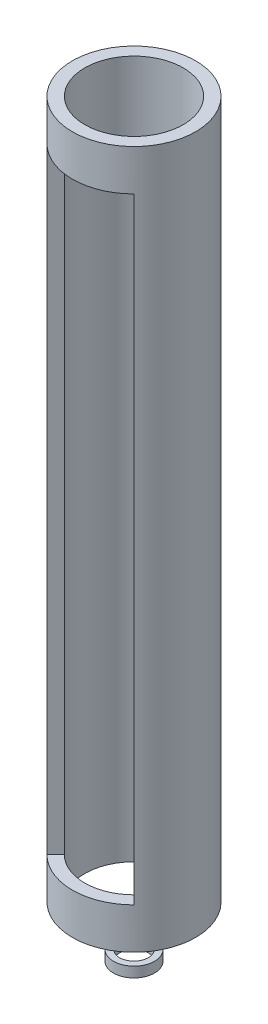
SolidWorks part; units mm, degrees
ref_plane "Front Plane" through (0, 0, 0) normal (0, 0, 1) x (1, 0, 0)
ref_plane "Top Plane" through (0, 0, 0) normal (0, 1, 0) x (1, 0, 0)
ref_plane "Right Plane" through (0, 0, 0) normal (1, 0, 0) x (0, 0, -1)
sketch "Sketch1" plane through (0, 0, 0) normal (0, 1, 0) x (1, 0, 0)
  line L0 (-8.4853, -8.4853) -> (-10.6066, -10.6066)
  line L1 (8.4853, -8.4853) -> (10.6066, -10.6066)
  circle A0 centre (0, 0) radius 15
  circle A1 centre (0, 0) radius 12
  circle A2 centre (0, 0) radius 5
  circle A3 centre (0, 0) radius 3.5
  dimension "D1" = 30
  dimension "D2" = 3
  dimension "D3" = 10
  dimension "D4" = 1.5
extrude "Inner Tube" add sketch "Sketch1" along normal blind 150 contours A1 L1 A0 L0 region at (-9.8248, 0, 9.267)
extrude "Bottom Extrude" add sketch "Sketch1<3>" against normal blind 10 contours A1 L0 A0 L1 | A1 L1 A0 L0 region at (0, 0, 12.2043) region at (-9.8248, 0, 9.267)
sketch "Sketch1<3>" plane through (0, 0, 0) normal (0, 1, 0) x (1, 0, 0) same geometry as "Sketch1"
extrude "Top Extrude" add sketch "Sketch1<4>" along normal blind 10 from surface contours A1 L0 A0 L1 | A1 L1 A0 L0 region at (0, 0, 12.2043) region at (-9.8248, 0, 9.267) starting at face at (0, 150, -1.977)
sketch "Sketch1<4>" plane through (0, 0, 0) normal (0, 1, 0) x (1, 0, 0) same geometry as "Sketch1"
extrude "Boss-Extrude4" add sketch "Sketch1<8>" against normal blind 2.5 from offset 20 separate body contours A2 A3 region at (-4.8586, 0, 0) offset against normal yes
sketch "Sketch1<8>" plane through (0, 0, 0) normal (0, 1, 0) x (1, 0, 0) same geometry as "Sketch1"
sketch "Infinite middle line" plane through (0, 0, 0) normal (0, 0, 1) x (1, 0, 0)
  line L0 (0, -1000) -> (0, 49000) construction
